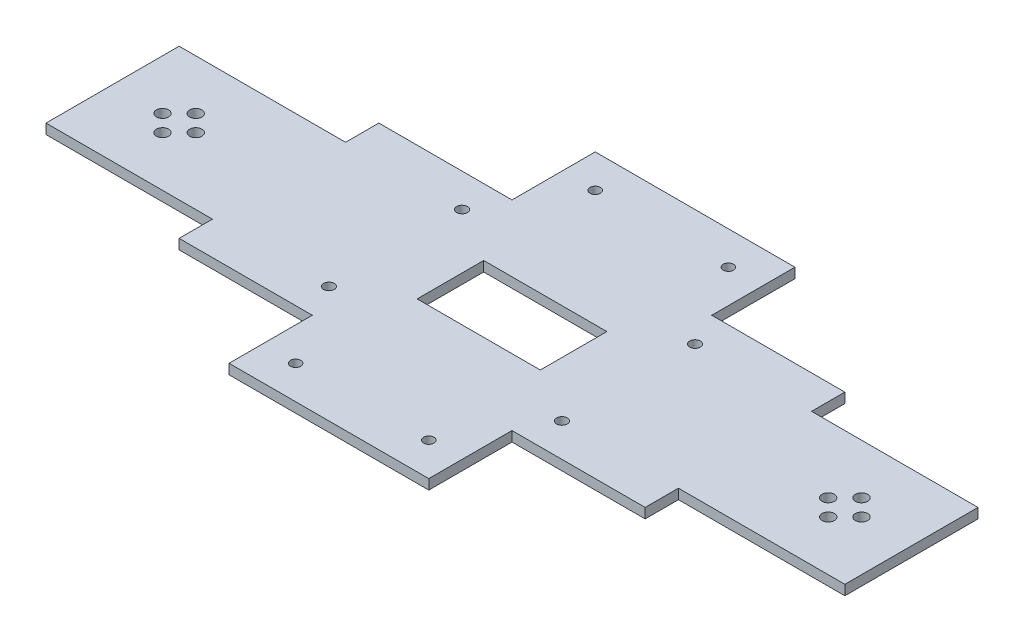
SolidWorks part; units mm, degrees
ref_plane "Front Plane" through (0, 0, 0) normal (0, 0, 1) x (1, 0, 0)
ref_plane "Top Plane" through (0, 0, 0) normal (0, 1, 0) x (1, 0, 0)
ref_plane "Right Plane" through (0, 0, 0) normal (1, 0, 0) x (0, 0, -1)
sketch "Sketch1" plane through (0, 0, 0) normal (0, 1, 0) x (1, 0, 0)
  line L0 (0, 50) -> (0, -43.3333) construction
  line L1 (120, 0) -> (100, 0) construction
  line L2 (-70, 30) -> (70, 30)
  line L3 (0, 30) -> (0, -30)
  line L4 (-70, -30) -> (70, -30)
  line L5 (70, 30) -> (70, -30)
  line L6 (70, 20) -> (120, 20)
  line L7 (70, 20) -> (70, -20)
  line L8 (70, -20) -> (120, -20)
  line L9 (120, 20) -> (120, -20)
  line L10 (120, 20) -> (70, 20) construction
  line L11 (100, 0) -> (120, 0) construction
  line L13 (120, 0) -> (100, 0) construction
  line L14 (100, 0) -> (100, 15) construction
  line L15 (-100, 0) -> (-100, 15) construction
  line L16 (-120, 0) -> (-100, 0) construction
  line L17 (-100, 0) -> (-120, 0) construction
  line L18 (-120, 20) -> (-70, 20) construction
  line L19 (-120, 0) -> (-100, 0) construction
  line L20 (-120, 20) -> (-120, -20)
  line L21 (-70, -20) -> (-120, -20)
  line L22 (-70, 20) -> (-70, -20)
  line L23 (-70, 20) -> (-120, 20)
  line L24 (-70, 30) -> (-70, -30)
  line L25 (-18.5, 10) -> (-18.5, -10)
  line L26 (-18.5, 10) -> (18.5, 10)
  line L27 (0, 10) -> (0, -10)
  line L28 (-18.5, -10) -> (18.5, -10)
  line L29 (18.5, 10) -> (18.5, -10)
  line L31 (0, 30) -> (32.0822, 30)
  line L32 (0, 30) -> (0, 55.2592)
  line L33 (0, 55.2592) -> (32.0822, 55.2592)
  line L34 (32.0822, 30) -> (32.0822, 55.2592)
  line L35 (0, -30) -> (32.0822, -30)
  line L36 (0, -30) -> (0, -49.982)
  line L37 (0, -49.982) -> (32.0822, -49.982)
  line L38 (32.0822, -30) -> (32.0822, -49.982)
  circle A0 centre (100, 5) radius 1.85
  circle A1 centre (105, 0) radius 1.85
  circle A2 centre (100, -5) radius 1.85
  circle A3 centre (95, 0) radius 1.85
  circle A4 centre (-95, 0) radius 1.85
  circle A5 centre (-100, -5) radius 1.85
  circle A6 centre (-105, 0) radius 1.85
  circle A7 centre (-100, 5) radius 1.85
  circle A8 centre (35, 20) radius 1.6
  circle A9 centre (35, -20) radius 1.6
  circle A10 centre (-35, -20) radius 1.6
  circle A11 centre (-35, 20) radius 1.6
  circle A12 centre (17.0822, -43) radius 1.55
  point P25 (100, 0)
  point P26 (70, -15)
  point P43 (-70, -15)
  point P44 (-100, 0)
  dimension "D8" = 3.7
  dimension "D9" = 5
  dimension "D11" = 5
  dimension "D12" = 5
  dimension "D13" = 30
  dimension "D14" = 10
  dimension "D7" = 35
  dimension "D17" = 20
  dimension "D18" = 3.2
  dimension "D19" = 3.2
  dimension "D20" = 40
  dimension "D21" = 3.1
  dimension "D22" = 15
  dimension "D23" = 13
  dimension "D1" = 30
  dimension "D2" = 30
  dimension "D3" = 10
  dimension "D4" = 10
  dimension "D5" = 70
  dimension "D6" = 50
  dimension "D15" = 10
  dimension "D16" = 18.5
  dimension "D10" = 4
extrude "Boss-Extrude1" add sketch "Sketch1" along normal blind 3 contours L5 L2 L3 L4 | L9 L6 L5 L8 A3 A2 A1 A0 | L22 L23 L20 L21 A6 A4 A5 A7 | L2 L24 L22 L4 L3 region at (-37.4981, 0, 0) region at (37.4981, 0, 0) region at (-70.6403, 0, 0) region at (95, 0, -19.3597)
sketch "Sketch2" plane through (0, 3, 0) normal (0, 1, 0) x (1, 0, 0)
  line L0 (-70, 30) -> (70, 30) construction
  line L1 (-30, 30) -> (30, 30)
  line L2 (0, 30) -> (0, 55)
  line L3 (-30, 55) -> (30, 55)
  line L4 (30, 30) -> (30, 55)
  line L5 (-70, -30) -> (70, -30) construction
  line L6 (-30, -30) -> (30, -30)
  line L7 (0, -30) -> (0, -55)
  line L8 (-30, -55) -> (30, -55)
  line L9 (30, -30) -> (30, -55)
  line L10 (0, 0) -> (0, -19.3557) construction
  line L11 (-30, -30) -> (-30, -55)
  line L12 (-30, 30) -> (-30, 55)
  line L13 (0, 0) -> (30, 0) construction
  circle A0 centre (20, -45) radius 1.55
  circle A2 centre (20, 45) radius 1.55
  circle A3 centre (-20, -45) radius 1.55
  circle A4 centre (-20, 45) radius 1.55
  line M6 (-70, -30) -> (70, -30)
  line M12 (70, 30) -> (-70, 30)
  dimension "D5" = 3.1
  dimension "D6" = 10
  dimension "D7" = 10
  dimension "D1" = 25
  dimension "D2" = 25
  dimension "D3" = 30
  dimension "D4" = 30
extrude "Boss-Extrude2" add sketch "Sketch2" against normal blind 3 contours L4 L3 L2 M12 | L12 L1 L2 L3 | L11 L8 L7 A3 M6 | L9 L6 L7 L8 A0 region at (-14.9492, 3, -42.4746) region at (14.9492, 3, -42.4746) region at (-14.9492, 3, 42.4746) region at (14.9492, 3, 42.4746)
